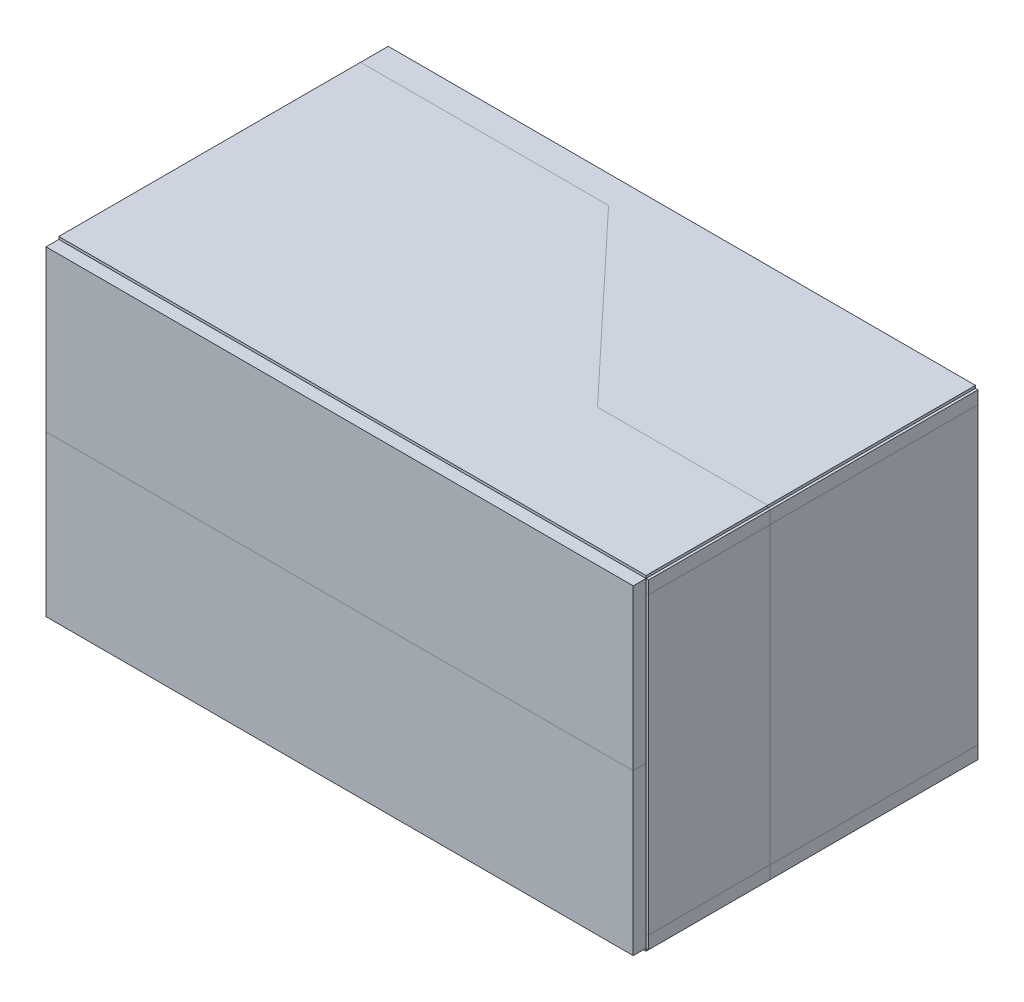
SolidWorks part; units mm, degrees
other "후면"
other "천장2"
other "천장1"
other "좌측면"
other "정면"
other "우측면"
other "바닥"
other "후면하단작음2"
other "후면상단작음2"
other "상단인테리어2"
other "하단인테리어2"
other "후면하단큼1"
other "후면상단큼1"
other "후면하단작음1"
other "후면상단작음1"
other "상단인테리어1"
other "하단인테리어1"
other "스크린홀더"
other "스크린"
other "스크린끝봉"
other "영사기 받침대"
other "영사기"
other "테이블"
other "리클라이너 의자1"
other "팔걸이1"
other "팔걸이2"
other "리클라이너 의자2"
other "팔걸이4"
other "팔걸이3"
other "스피커1"
other "스피커2"
other "스피커3"
other "스탠드스피커1"
ref_plane "정면" through (0, 0, 0) normal (0, 0, 1) x (1, 0, 0)
ref_plane "윗면" through (0, 0, 0) normal (0, 1, 0) x (1, 0, 0)
ref_plane "우측면" through (0, 0, 0) normal (1, 0, 0) x (0, 0, -1)
sketch "스케치1" plane through (0, 0, 0) normal (0, 0, 1) x (1, 0, 0)
  line L1 (51, 74.896) -> (280, 74.896)
  line L2 (51, 74.896) -> (51, -50)
  line L3 (51, -50) -> (280, -50)
  line L4 (280, 74.896) -> (280, -50)
extrude "보스-돌출1" add sketch "스케치1" along normal up to surface (7.8606 mm away)
sketch "스케치2" plane through (0, 0, 7.8606) normal (0, 0, 1) x (1, 0, 0)
  line L0 (280, 74.896) -> (280, -50) construction
  line L1 (51, 74.896) -> (280, 74.896)
  line L2 (51, 74.896) -> (51, 69.896)
  line L3 (51, 69.896) -> (280, 69.896)
  line L4 (280, 74.896) -> (280, 69.896)
  dimension "D1" = 5
extrude "컷-돌출1" cut sketch "스케치2" against normal up to surface (7.8606 mm away) contours L1 L3 L2 up to face at (165.5, 12.448, 0)
sketch "스케치4" plane through (0, 0, 7.8606) normal (0, 0, 1) x (1, 0, 0)
  line L0 (280, 69.896) -> (280, -50) construction
  line L1 (51, -50) -> (280, -50)
  line L2 (51, -50) -> (51, -45)
  line L3 (51, -45) -> (280, -45)
  line L4 (280, -50) -> (280, -45)
  line M1 (280, -50) -> (280, 69.896)
  line M3 (51, 69.896) -> (51, -50)
  line M4 (51, -50) -> (280, -50)
  dimension "D1" = 5
extrude "컷-돌출2" cut sketch "스케치4" against normal up to surface (7.8606 mm away) contours L3 M3 M4 M1 up to face at (165.5, 9.948, 0)
sketch "스케치5" plane through (0, 0, 7.8606) normal (0, 0, 1) x (1, 0, 0)
  line L0 (51, -45) -> (280, -45) construction
  line L1 (280, 69.896) -> (275, 69.896)
  line L2 (280, 69.896) -> (280, -45)
  line L3 (280, -45) -> (275, -45)
  line L4 (275, 69.896) -> (275, -45)
  line M1 (51, -45) -> (280, -45)
  line M2 (280, -45) -> (280, 69.896)
  line M3 (280, 69.896) -> (51, 69.896)
  dimension "D1" = 5
extrude "컷-돌출3" cut sketch "스케치5" against normal up to surface (7.8606 mm away) contours L4 M3 M1 M2 up to face at (165.5, 12.448, 0)
sketch "스케치6" plane through (0, 69.896, 0) normal (0, 1, 0) x (1, 0, 0)
  line L1 (51, 0) -> (280, 0)
  line L2 (51, 0) -> (51, -128.4421)
  line L3 (51, -128.4421) -> (280, -128.4421)
  line L4 (280, 0) -> (280, -128.4421)
extrude "보스-돌출3" add sketch "스케치6" along normal blind 5 separate body
sketch "스케치7" plane through (0, 0, 7.8606) normal (0, 0, 1) x (1, 0, 0)
  line L0 (51, -45) -> (275, -45) construction
  line L1 (51, 69.896) -> (56, 69.896)
  line L2 (51, 69.896) -> (51, -45)
  line L3 (51, -45) -> (56, -45)
  line L4 (56, 69.896) -> (56, -45)
  dimension "D1" = 5
extrude "보스-돌출4" add sketch "스케치7" along normal up to surface (120.5815 mm away) separate body up to face at (165.5, 72.396, 128.4421)
sketch "스케치8" plane through (0, -45, 0) normal (0, -1, 0) x (1, 0, 0)
  line L1 (51, 128.4421) -> (280, 128.4421)
  line L2 (51, 128.4421) -> (51, 0)
  line L3 (51, 0) -> (280, 0)
  line L4 (280, 128.4421) -> (280, 0)
extrude "보스-돌출5" add sketch "스케치8" along normal blind 5 separate body
sketch "스케치9" plane through (0, 0, 128.4421) normal (0, 0, 1) x (1, 0, 0)
  line L1 (51, 74.896) -> (280, 74.896)
  line L2 (51, 74.896) -> (51, 12.446)
  line L3 (51, 12.446) -> (280, 12.446)
  line L4 (280, 74.896) -> (280, 12.446)
  dimension "D1" = 62.45
extrude "보스-돌출6" add sketch "스케치9" along normal blind 5 separate body
sketch "스케치10" plane through (0, 0, 128.4421) normal (0, 0, 1) x (1, 0, 0)
  line L1 (51, 12.446) -> (280, 12.446)
  line L2 (51, 12.446) -> (51, -50)
  line L3 (51, -50) -> (280, -50)
  line L4 (280, 12.446) -> (280, -50)
extrude "보스-돌출7" add sketch "스케치10" along normal blind 5 separate body
sketch "스케치11" plane through (275, 0, 0) normal (1, 0, 0) x (0, 0, -1)
  line L1 (0, -45) -> (-128.4421, -45)
  line L2 (0, -45) -> (0, 69.896)
  line L3 (0, 69.896) -> (-128.4421, 69.896)
  line L4 (-128.4421, -45) -> (-128.4421, 69.896)
extrude "보스-돌출8" add sketch "스케치11" along normal blind 5 separate body
sketch "스케치12" plane through (0, -50, 0) normal (0, -1, 0) x (1, 0, 0)
  line L0 (51, 10.7712) -> (147.7059, 10.7712)
  line L1 (51, 128.4421) -> (51, 0) construction
  line L2 (147.7059, 10.7712) -> (213.6585, 81.0356)
  line L3 (213.6585, 81.0356) -> (280, 81.0356)
  line L4 (280, 0) -> (280, 128.4421) construction
  line L5 (51, 10.7712) -> (51, 0)
  line L6 (51, 0) -> (280, 0)
  line L7 (280, 0) -> (280, 81.0356)
extrude "보스-돌출9" add sketch "스케치12" along normal blind 1 separate body
sketch "스케치13" plane through (0, -50, 0) normal (0, -1, 0) x (1, 0, 0)
  line L0 (51, 128.4421) -> (51, 10.7712)
  line L1 (51, 10.7712) -> (147.7059, 10.7712)
  line L2 (147.7059, 10.7712) -> (213.6585, 81.0356)
  line L3 (213.6585, 81.0356) -> (280, 81.0356)
  line L4 (280, 81.0356) -> (280, 128.4421)
  line L5 (280, 128.4421) -> (51, 128.4421)
extrude "보스-돌출10" add sketch "스케치13" along normal blind 1 separate body
sketch "스케치14" plane through (280, 0, 0) normal (1, 0, 0) x (0, 0, -1)
  line L1 (-81.0356, -50) -> (-128.4421, -50)
  line L2 (-81.0356, -50) -> (-81.0356, -45)
  line L3 (-81.0356, -45) -> (-128.4421, -45)
  line L4 (-128.4421, -50) -> (-128.4421, -45)
extrude "보스-돌출11" add sketch "스케치14" along normal blind 1 separate body
sketch "스케치15" plane through (280, 0, 0) normal (1, 0, 0) x (0, 0, -1)
  line L1 (-81.0356, -50) -> (0, -50)
  line L2 (-81.0356, -50) -> (-81.0356, -45)
  line L3 (-81.0356, -45) -> (0, -45)
  line L4 (0, -50) -> (0, -45)
extrude "보스-돌출12" add sketch "스케치15" along normal blind 1 separate body
sketch "스케치16" plane through (280, 0, 0) normal (1, 0, 0) x (0, 0, -1)
  line L0 (-128.4421, 69.896) -> (0, 69.896) construction
  line L1 (-128.4421, -45) -> (-81.0356, -45)
  line L2 (-128.4421, -45) -> (-128.4421, 69.896)
  line L3 (-128.4421, 69.896) -> (-81.0356, 69.896)
  line L4 (-81.0356, -45) -> (-81.0356, 69.896)
extrude "보스-돌출13" add sketch "스케치16" along normal blind 1 separate body
sketch "스케치17" plane through (280, 0, 0) normal (1, 0, 0) x (0, 0, -1)
  line L0 (0, 74.896) -> (0, 69.896) construction
  line L1 (-81.0356, -45) -> (0, -45)
  line L2 (-81.0356, -45) -> (-81.0356, 69.896)
  line L3 (-81.0356, 69.896) -> (0, 69.896)
  line L4 (0, -45) -> (0, 69.896)
  line L5 (-128.4421, 69.896) -> (0, 69.896) construction
extrude "보스-돌출14" add sketch "스케치17" along normal blind 1 separate body
ref_plane "평면1" through (0, 12.446, 0) normal (0, 1, 0) x (1, 0, 0)
mirror "대칭 복사2" about plane through (0, 12.446, 0) normal (0, 1, 0) of bodies 112 113 114 115
other "바디 저장1"
other "바디 저장2"
sketch "스케치18" plane through (56, 0, 0) normal (1, 0, 0) x (0, 0, -1)
  line L0 (-128.4421, 69.896) -> (-7.8606, 69.896) construction
  line L1 (-124.4421, -40.104) -> (-114.4421, -40.104)
  line L2 (-124.4421, -40.104) -> (-124.4421, 64.896)
  line L3 (-124.4421, 64.896) -> (-114.4421, 64.896)
  line L4 (-114.4421, -40.104) -> (-114.4421, 64.896)
  line L5 (-128.4421, 69.896) -> (-128.4421, -45) construction
  dimension "D1" = 105
  dimension "D2" = 5
  dimension "D3" = 4
  dimension "D4" = 10
extrude "보스-돌출15" add sketch "스케치18" along normal blind 10 separate body
sketch "스케치19" plane through (0, 0, 114.4421) normal (0, 0, -1) x (-1, 0, 0)
  line L0 (-66, 64.896) -> (-56, 64.896) construction
  line L1 (-63, 61.896) -> (-62, 61.896)
  line L2 (-63, 61.896) -> (-63, -37.104)
  line L3 (-63, -37.104) -> (-62, -37.104)
  line L4 (-62, 61.896) -> (-62, -37.104)
  line L5 (-66, -40.104) -> (-56, -40.104) construction
  line L6 (-66, -40.104) -> (-66, 64.896) construction
  dimension "D1" = 3
  dimension "D2" = 3
  dimension "D3" = 3
  dimension "D4" = 1
extrude "보스-돌출16" add sketch "스케치19" along normal blind 77 separate body contours L2 L3 L4 L1
sketch "스케치20" plane through (0, -37.104, 0) normal (0, -1, 0) x (1, 0, 0)
  line L0 (63, 37.4421) -> (62, 37.4421) construction
  circle A0 centre (62.5, 37.4421) radius 0.75
  dimension "D1" = 1.5
extrude "보스-돌출17" add sketch "스케치20" along normal blind 3 and the other way blind 101 separate body
sketch "스케치21" plane through (0, 0, 7.8606) normal (0, 0, 1) x (1, 0, 0)
  line L0 (97.5445, 69.896) -> (97.5445, -45) construction
  line L1 (51, 69.896) -> (280, 69.896) construction
  line L2 (51, -45) -> (275, -45) construction
  line L4 (93.5445, 16.448) -> (101.5445, 16.448)
  line L5 (93.5445, 16.448) -> (93.5445, 8.448)
  line L6 (93.5445, 8.448) -> (101.5445, 8.448)
  line L7 (101.5445, 16.448) -> (101.5445, 8.448)
  line L8 (93.5445, 16.448) -> (101.5445, 8.448) construction
  line L9 (93.5445, 8.448) -> (101.5445, 16.448) construction
  point P6 (97.5445, 12.448)
  dimension "D1" = 8
  dimension "D2" = 8
extrude "보스-돌출18" add sketch "스케치21" along normal blind 30 separate body
sketch "스케치22" plane through (0, 0, 37.8606) normal (0, 0, 1) x (1, 0, 0)
  line L0 (97.5445, 8.448) -> (97.5445, 16.448) construction
  line L1 (93.5445, 8.448) -> (101.5445, 8.448) construction
  line L2 (101.5445, 16.448) -> (93.5445, 16.448) construction
  line L4 (82.5445, 22.448) -> (112.5445, 22.448)
  line L5 (82.5445, 22.448) -> (82.5445, 2.448)
  line L6 (82.5445, 2.448) -> (112.5445, 2.448)
  line L7 (112.5445, 22.448) -> (112.5445, 2.448)
  line L8 (82.5445, 22.448) -> (112.5445, 2.448) construction
  line L9 (82.5445, 2.448) -> (112.5445, 22.448) construction
  point P6 (97.5445, 12.448)
  dimension "D1" = 20
  dimension "D2" = 30
extrude "보스-돌출19" add sketch "스케치22" along normal blind 3
sketch "스케치23" plane through (0, 0, 40.8606) normal (0, 0, 1) x (1, 0, 0)
  line L0 (111.5445, 21.448) -> (83.5445, 21.448)
  line L1 (83.5445, 21.448) -> (83.5445, 3.448)
  line L2 (83.5445, 3.448) -> (111.5445, 3.448)
  line L3 (111.5445, 3.448) -> (111.5445, 21.448)
  line L4 (112.5445, 2.448) -> (112.5445, 22.448)
  line L5 (112.5445, 22.448) -> (82.5445, 22.448)
  line L6 (82.5445, 22.448) -> (82.5445, 2.448)
  line L7 (82.5445, 2.448) -> (112.5445, 2.448)
  line L8 (112.5445, 2.448) -> (112.5445, 22.448)
  line L9 (112.5445, 22.448) -> (82.5445, 22.448)
  line L10 (82.5445, 22.448) -> (82.5445, 2.448)
  line L11 (82.5445, 2.448) -> (112.5445, 2.448)
  dimension "D1" = 0
  dimension "D2" = 1
extrude "컷-돌출4" cut sketch "스케치23" against normal blind 2 contours L2 L3 L0 L1
sketch "스케치24" plane through (0, 0, 38.8606) normal (0, 0, 1) x (1, 0, 0)
  line L0 (97.5445, 22.448) -> (97.5445, 2.448) construction
  line L1 (112.5445, 22.448) -> (82.5445, 22.448) construction
  line L2 (82.5445, 2.448) -> (112.5445, 2.448) construction
  line L4 (85.0445, 19.948) -> (110.0445, 19.948)
  line L5 (85.0445, 19.948) -> (85.0445, 4.948)
  line L6 (85.0445, 4.948) -> (110.0445, 4.948)
  line L7 (110.0445, 19.948) -> (110.0445, 4.948)
  line L8 (85.0445, 19.948) -> (110.0445, 4.948) construction
  line L9 (85.0445, 4.948) -> (110.0445, 19.948) construction
  point P6 (97.5445, 12.448)
  dimension "D1" = 25
  dimension "D2" = 15
extrude "보스-돌출20" add sketch "스케치24" along normal blind 12 separate body
sketch "스케치25" plane through (0, 4.948, 0) normal (0, -1, 0) x (1, 0, 0)
  line L0 (92.9297, 50.8606) -> (104.0121, 46.12) construction
  line L1 (85.0445, 50.8606) -> (110.0445, 50.8606) construction
  line L2 (94.4486, 54.4113) -> (105.531, 49.6707)
  line L3 (91.4109, 47.31) -> (102.4933, 42.5693)
  arc A0 (94.4486, 54.4113) -> (91.4109, 47.31) centre (92.9297, 50.8606) ccw
  arc A1 (102.4933, 42.5693) -> (105.531, 49.6707) centre (104.0121, 46.12) ccw
  point P4 (98.4709, 48.4903)
  dimension "D1" = 7.7238
  dimension "D2" = 12.0538
extrude "컷-돌출5" cut sketch "스케치25" against normal blind 22
sketch "스케치27" plane through (0, 0, 7.8606) normal (0, 0, 1) x (1, 0, 0)
  line L0 (275, 12.448) -> (51, 12.448) construction
  line L1 (275, 69.896) -> (275, -45) construction
  line L2 (51, -45) -> (51, 69.896) construction
  line L4 (202.8264, 14.948) -> (207.8264, 14.948)
  line L5 (202.8264, 14.948) -> (202.8264, 9.948)
  line L6 (202.8264, 9.948) -> (207.8264, 9.948)
  line L7 (207.8264, 14.948) -> (207.8264, 9.948)
  line L8 (202.8264, 14.948) -> (207.8264, 9.948) construction
  line L9 (202.8264, 9.948) -> (207.8264, 14.948) construction
  point P6 (205.3264, 12.448)
  dimension "D1" = 5
  dimension "D2" = 5
extrude "보스-돌출21" add sketch "스케치27" along normal blind 35 separate body
sketch "스케치28" plane through (0, 0, 7.8606) normal (0, 0, 1) x (1, 0, 0)
  line L0 (51, -45) -> (275, -45) construction
  line L1 (163.592, -45) -> (253.592, -45)
  line L2 (163.592, -45) -> (163.592, -9.1297)
  line L3 (163.592, -9.1297) -> (253.592, -9.1297)
  line L4 (253.592, -45) -> (253.592, -9.1297)
  dimension "D1" = 90
extrude "보스-돌출22" add sketch "스케치28" along normal blind 70 separate body
sketch "스케치29" plane through (0, -45, 0) normal (0, -1, 0) x (1, 0, 0)
  line L4 (163.592, 7.8606) -> (253.592, 7.8606)
  line L5 (253.592, 7.8606) -> (253.592, 77.8606)
  line L6 (253.592, 77.8606) -> (163.592, 77.8606)
  line L7 (163.592, 77.8606) -> (163.592, 7.8606)
  line L8 (163.592, 7.8606) -> (253.592, 7.8606)
  line L9 (253.592, 7.8606) -> (253.592, 77.8606)
  line L10 (253.592, 77.8606) -> (163.592, 77.8606)
  line L11 (163.592, 77.8606) -> (163.592, 7.8606)
  dimension "D1" = 0
extrude "컷-돌출6" cut sketch "스케치29" against normal blind 5
sketch "스케치30" plane through (0, -40, 0) normal (0, -1, 0) x (1, 0, 0)
  line L0 (163.592, 24.8973) -> (192.0223, 42.8606)
  line L1 (163.592, 77.8606) -> (163.592, 7.8606) construction
  line L2 (192.0223, 42.8606) -> (219.8472, 42.8606)
  line L3 (219.8472, 42.8606) -> (253.592, 70.3172)
  line L4 (253.592, 7.8606) -> (253.592, 77.8606) construction
  line L5 (253.592, 70.3172) -> (253.592, 7.8606)
  line L6 (253.592, 7.8606) -> (163.592, 7.8606)
  line L7 (163.592, 7.8606) -> (163.592, 24.8973)
  line M7 (163.592, 77.8606) -> (163.592, 7.8606)
  line M9 (253.592, 7.8606) -> (253.592, 77.8606)
  line M10 (253.592, 77.8606) -> (163.592, 77.8606)
extrude "컷-돌출7" cut sketch "스케치30" against normal blind 35 contours L2 L3 L0 M9 M10 M7
sketch "스케치31" plane through (0, -40, 0) normal (0, -1, 0) x (1, 0, 0)
  line L0 (192.0223, 42.8606) -> (219.8472, 42.8606) construction
  line L1 (192.0223, 50.3606) -> (219.8472, 50.3606)
  line L2 (192.0223, 35.3606) -> (219.8472, 35.3606)
  arc A0 (192.0223, 50.3606) -> (192.0223, 35.3606) centre (192.0223, 42.8606) ccw
  arc A1 (219.8472, 35.3606) -> (219.8472, 50.3606) centre (219.8472, 42.8606) ccw
  point P4 (205.9347, 42.8606)
  dimension "D1" = 15
  dimension "D2" = 27.8248
extrude "보스-돌출23" add sketch "스케치31" along normal blind 5 separate body
sketch "스케치32" plane through (66.5882, 0, -81.8387) normal (-0.6311, 0, 0.7757) x (0.7757, 0, 0.6311)
  line L0 (241.0848, -24.5648) -> (197.581, -24.5648) construction
  line L1 (241.0848, -9.1297) -> (226.0848, -9.1297)
  line L2 (241.0848, -9.1297) -> (241.0848, -14.1297)
  line L3 (241.0848, -14.1297) -> (226.0848, -14.1297)
  line L4 (226.0848, -9.1297) -> (226.0848, -14.1297)
  line L5 (241.0848, -9.1297) -> (241.0848, -40) construction
  line L6 (197.581, -9.1297) -> (197.581, -40) construction
  line L7 (226.0848, -40) -> (226.0848, -35)
  line L8 (241.0848, -35) -> (226.0848, -35)
  line L9 (241.0848, -40) -> (226.0848, -40)
  line L10 (241.0848, -40) -> (241.0848, -35)
  dimension "D1" = 15
  dimension "D2" = 5
extrude "보스-돌출24" add sketch "스케치32" along normal blind 5
sketch "스케치33" plane through (66.5882, 0, -81.8387) normal (-0.6311, 0, 0.7757) x (0.7757, 0, 0.6311)
  line L0 (233.5848, -14.1297) -> (233.5848, -35) construction
  line L5 (226.0848, -14.1297) -> (241.0848, -14.1297) construction
  line L6 (241.0848, -35) -> (226.0848, -35) construction
  line L8 (230.0848, -18.5648) -> (237.0848, -18.5648)
  line L9 (230.0848, -18.5648) -> (230.0848, -30.5648)
  line L10 (230.0848, -30.5648) -> (237.0848, -30.5648)
  line L11 (237.0848, -18.5648) -> (237.0848, -30.5648)
  line L12 (230.0848, -18.5648) -> (237.0848, -30.5648) construction
  line L13 (230.0848, -30.5648) -> (237.0848, -18.5648) construction
  point P0 (233.5848, -24.5648)
  dimension "D1" = 7
  dimension "D2" = 12
extrude "보스-돌출25" add sketch "스케치33" along normal blind 3
fillet "필렛1" radius 3 1 edges at (252.0142, -14.1297, 72.2564)
fillet "필렛2" radius 3 1 edges at (240.3791, -14.1297, 62.7894)
fillet "필렛3" radius 3 1 edges at (240.3791, -35, 62.7894)
fillet "필렛4" radius 3 1 edges at (252.0142, -35, 72.2564)
fillet "필렛5" radius 3 8 edges at (249.5426, -30.5648, 68.9562) (249.5426, -18.5648, 68.9562) (244.1129, -18.5648, 64.5383) (244.1129, -30.5648, 64.5383) (248.5959, -24.5648, 70.1197) (245.8811, -18.5648, 67.9108) (243.1662, -24.5648, 65.7018) (245.8811, -30.5648, 67.9108)
ref_plane "평면2" through (0, -24.5648, 0) normal (0, 1, 0) x (1, 0, 0)
mirror "대칭 복사3" about plane through (0, -24.5648, 0) normal (0, 1, 0) of bodies 170
sketch "스케치35" plane through (35.4328, 0, -56.0788) normal (-0.5342, 0, 0.8454) x (0.8454, 0, 0.5342)
  line L0 (151.5979, -9.1297) -> (185.2277, -9.1297) construction
  line L1 (151.5979, -40) -> (155.5979, -40)
  line L2 (151.5979, -40) -> (151.5979, -9.1297)
  line L3 (151.5979, -9.1297) -> (155.5979, -9.1297)
  line L4 (155.5979, -40) -> (155.5979, -9.1297)
  dimension "D1" = 4
extrude "보스-돌출26" add sketch "스케치35" along normal blind 6
ref_plane "평면3" through (0, 12.448, 0) normal (0, -1, 0) x (-1, 0, 0)
mirror "대칭 복사4" about plane through (0, 12.448, 0) normal (0, -1, 0) of bodies 174 170 173
sketch "스케치38" plane through (0, 0, 42.8606) normal (0, 0, 1) x (1, 0, 0)
  line L0 (205.3264, 14.948) -> (205.3264, 9.948) construction
  line L1 (182.3264, 26.948) -> (228.3264, 26.948)
  line L2 (182.3264, 26.948) -> (182.3264, -2.052)
  line L3 (182.3264, -2.052) -> (228.3264, -2.052)
  line L4 (228.3264, 26.948) -> (228.3264, -2.052)
  line L5 (182.3264, 26.948) -> (228.3264, -2.052) construction
  line L6 (182.3264, -2.052) -> (228.3264, 26.948) construction
  line L7 (207.8264, 14.948) -> (202.8264, 14.948) construction
  line L8 (202.8264, 9.948) -> (207.8264, 9.948) construction
  point P0 (205.3264, 12.448)
  dimension "D1" = 29
  dimension "D2" = 46
extrude "보스-돌출27" add sketch "스케치38" along normal blind 6
sketch "스케치39" plane through (0, 0, 48.8606) normal (0, 0, 1) x (1, 0, 0)
  line L0 (183.3264, 25.948) -> (183.3264, -1.052)
  line L1 (183.3264, -1.052) -> (227.3264, -1.052)
  line L2 (227.3264, -1.052) -> (227.3264, 25.948)
  line L3 (227.3264, 25.948) -> (183.3264, 25.948)
  line L4 (228.3264, -2.052) -> (228.3264, 26.948)
  line L5 (228.3264, 26.948) -> (182.3264, 26.948)
  line L6 (182.3264, 26.948) -> (182.3264, -2.052)
  line L7 (182.3264, -2.052) -> (228.3264, -2.052)
  line L8 (228.3264, -2.052) -> (228.3264, 26.948)
  line L9 (228.3264, 26.948) -> (182.3264, 26.948)
  line L10 (182.3264, 26.948) -> (182.3264, -2.052)
  line L11 (182.3264, -2.052) -> (228.3264, -2.052)
  dimension "D1" = 0
  dimension "D2" = 1
extrude "컷-돌출8" cut sketch "스케치39" against normal blind 3 contours L2 L3 L0 L1
sketch "스케치40" plane through (0, 69.896, 0) normal (0, -1, 0) x (1, 0, 0)
  line L0 (51, 128.4421) -> (280, 128.4421) construction
  line L1 (90.7138, 128.4421) -> (125.7138, 128.4421)
  line L2 (90.7138, 128.4421) -> (90.7138, 108.4421)
  line L3 (90.7138, 108.4421) -> (125.7138, 108.4421)
  line L4 (125.7138, 128.4421) -> (125.7138, 108.4421)
  dimension "D1" = 35
  dimension "D2" = 20
extrude "보스-돌출28" add sketch "스케치40" along normal blind 15 separate body
fillet "필렛6" radius 3 1 edges at (108.2138, 54.896, 108.4421)
pattern_linear "선형 패턴1" count 3 spacing 60 along (1, 0, 0) of bodies 180
sketch "스케치41" plane through (0, 0, 7.8606) normal (0, 0, 1) x (1, 0, 0)
  line L0 (77.1861, -29.3184) -> (90.2536, -44.4647)
  line L1 (77.1861, -29.3184) -> (83.4523, -23.9123)
  line L2 (90.2536, -44.4647) -> (96.5198, -39.0586)
  line L3 (83.4523, -23.9123) -> (96.5198, -39.0586)
  line L4 (77.1861, -29.3184) -> (96.5198, -39.0586) construction
  line L5 (90.2536, -44.4647) -> (83.4523, -23.9123) construction
  point P1 (86.8529, -34.1885)
extrude "보스-돌출29" add sketch "스케치41" along normal blind 55 separate body
sketch "스케치42" plane through (36.0151, 31.0718, 0) normal (0.7572, 0.6532, 0) x (0, 0, -1)
  line L0 (-62.8606, -82.6213) -> (-7.8606, -82.6213) construction
  line L1 (-62.8606, -92.6234) -> (-62.8606, -72.6192) construction
  line L2 (-7.8606, -92.6234) -> (-7.8606, -72.6192) construction
  circle A1 centre (-50.6082, -82.6213) radius 7.5
  circle A2 centre (-32.6082, -82.6213) radius 7.5
  dimension "D1" = 15
  dimension "D2" = 2
extrude "컷-돌출9" cut sketch "스케치42" against normal blind 5 draft 30
sketch "스케치43" plane through (32.2293, 27.8057, 0) normal (0.7572, 0.6532, 0) x (0, 0, -1)
  circle A1 centre (-50.6082, -82.6213) radius 4.6132
  circle A2 centre (-50.6082, -82.6213) radius 4.6132
  circle A3 centre (-32.6082, -82.6213) radius 4.6132
  circle A4 centre (-32.6082, -82.6213) radius 4.6132
  dimension "D1" = 0
  dimension "D2" = 0
extrude "보스-돌출30" add sketch "스케치43" along normal blind 5
mirror "대칭 복사5" about plane through (0, 12.448, 0) normal (0, -1, 0) of bodies 185
